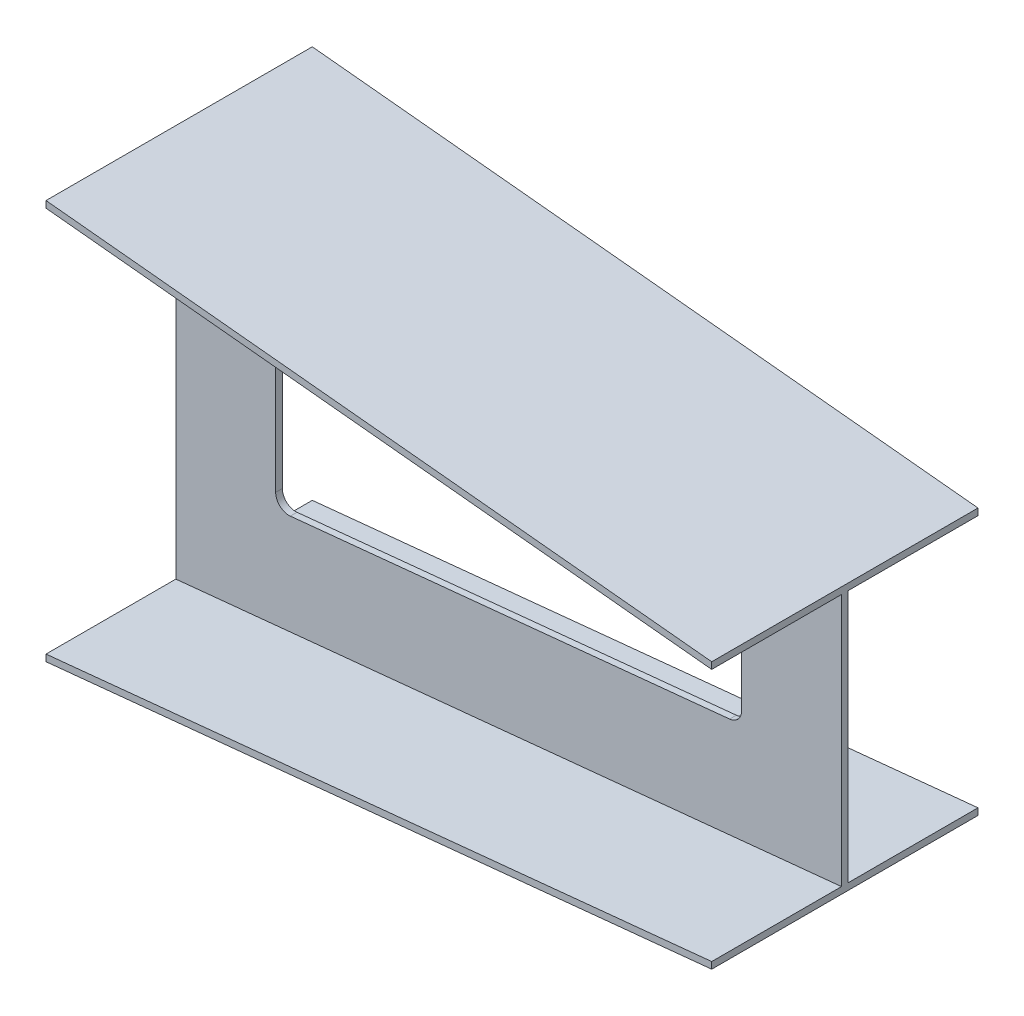
SolidWorks part; units mm, degrees
ref_plane "Front Plane" through (0, 0, 0) normal (0, 0, 1) x (1, 0, 0)
ref_plane "Top Plane" through (0, 0, 0) normal (0, 1, 0) x (1, 0, 0)
ref_plane "Right Plane" through (0, 0, 0) normal (1, 0, 0) x (0, 0, -1)
sketch "Sketch1" plane through (0, 0, 0) normal (1, 0, 0) x (0, 0, -1)
  line L1 (-205, 300) -> (195, 300)
  line L2 (-205, 300) -> (-205, 290)
  line L4 (195, 300) -> (195, 290)
  line L6 (-205, -290) -> (-205, -300)
  line L7 (-205, -300) -> (195, -300)
  line L8 (195, -290) -> (195, -300)
  line L15 (-205, -290) -> (-10, -290)
  line L16 (-5, 290) -> (-5, -690) construction
  line L18 (-205, 290) -> (-10, 290)
  line L19 (0, 0) -> (192.2403, 0) construction
  line L21 (-10, 290) -> (-10, -290)
  line L23 (0, 290) -> (0, -290)
  line L27 (0, 290) -> (195, 290)
  line L28 (0, -290) -> (195, -290)
  dimension "D1" = 400
  dimension "D2" = 10
  dimension "D3" = 600
  dimension "D4" = 10
ref_plane "Plane2" through (1000, 0, 0) normal (1, 0, 0) x (0, 0, -1)
sketch "Sketch4" plane through (1000, 0, -1000) normal (-1, 0, 0) x (0, 0, 1)
  line L1 (805, 200) -> (1205, 200)
  line L2 (805, 200) -> (805, 190)
  line L4 (1205, 200) -> (1205, 190)
  line L6 (805, -190) -> (805, -200)
  line L7 (805, -200) -> (1205, -200)
  line L8 (1205, -190) -> (1205, -200)
  line L15 (805, -190) -> (1000, -190)
  line L16 (1005, 390) -> (1005, -390) construction
  line L18 (805, 190) -> (1000, 190)
  line L19 (1010, -190) -> (1205, -190)
  line L21 (1000, 190) -> (1000, -190)
  line L23 (1010, 190) -> (1010, -190)
  line L24 (1010, 190) -> (1205, 190)
  line L26 (1010, 290) -> (1010, -290) construction
  line L27 (1000, 0) -> (820.2065, 0) construction
  dimension "D1" = 400
  dimension "D2" = 10
  dimension "D3" = 400
  dimension "D4" = 10
loft "Loft4" add profiles "Sketch1", "Sketch4" connector at (0, 290, 10) connector at (1000, 190, 10)
sketch "Sketch6" plane through (0, 0, 10) normal (0, 0, 1) x (1, 0, 0)
  line L8 (150, -124.2519) -> (850, -54.2519)
  line L9 (850, -54.2519) -> (850, 54.2519)
  line L10 (850, 54.2519) -> (150, 124.2519)
  line L11 (150, 124.2519) -> (150, -124.2519)
  line L12 (171.9901, -122.0529) -> (831.9901, -56.0529)
  line L13 (850, -36.1521) -> (850, 36.1521)
  line L14 (831.9901, 56.0529) -> (171.9901, 122.0529)
  line L15 (150, 102.1521) -> (150, -102.1521)
  arc A0 (150, -102.1521) -> (171.9901, -122.0529) centre (170, -102.1521) ccw
  arc A1 (850, 36.1521) -> (831.9901, 56.0529) centre (830, 36.1521) ccw
  arc A2 (850, -36.1521) -> (831.9901, -56.0529) centre (830, -36.1521) cw
  arc A3 (150, 102.1521) -> (171.9901, 122.0529) centre (170, 102.1521) cw
  dimension "D2" = 20
  dimension "D1" = 150
extrude "Cut-Extrude1" cut sketch "Sketch6" against normal blind 10
equation "\"ANS_h2\"=400"
equation "\"D3@Sketch4\"=\"ANS_h2\""
equation "\"ANS_w2\"=400"
equation "\"D1@Sketch4\"=\"ANS_w2\""
equation "\"ANS_h3\"=600"
equation "\"D3@Sketch1\"=\"ANS_h3\""
equation "\"ANS_w3\"=400"
equation "\"D1@Sketch1\"=\"ANS_w3\""
